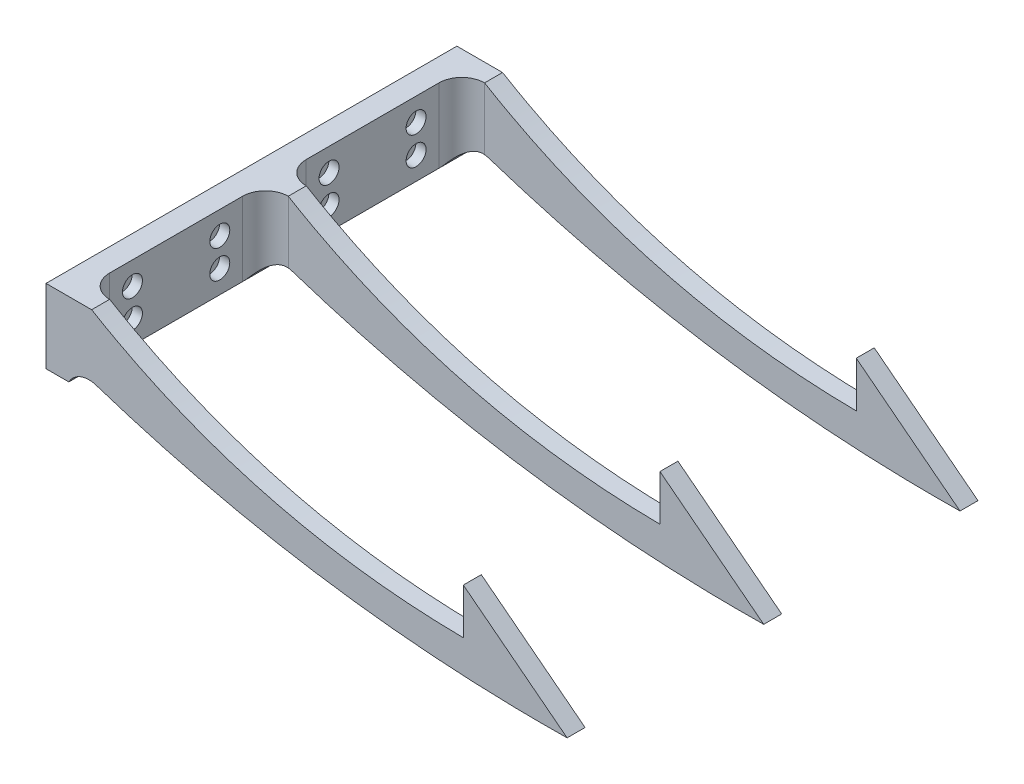
SolidWorks part; units mm, degrees
ref_plane "Front Plane" through (0, 0, 0) normal (0, 0, 1) x (1, 0, 0)
ref_plane "Top Plane" through (0, 0, 0) normal (0, 1, 0) x (1, 0, 0)
ref_plane "Right Plane" through (0, 0, 0) normal (1, 0, 0) x (0, 0, -1)
sketch "Sketch1" plane through (0, 0, 0) normal (0, 0, 1) x (1, 0, 0)
  line L0 (0, -6.35) -> (0, 6.35)
  line L1 (0, 6.35) -> (12.7, 6.35)
  line L2 (116.0939, -20.9749) -> (116.0939, -8.2749)
  line L3 (116.0939, -8.2749) -> (144.9605, -30.6605)
  line L5 (0, 12.7) -> (0, -12.7) construction
  line L6 (0, -12.7) -> (17.9605, -30.6605) construction
  line L7 (17.9605, -30.6605) -> (144.9605, -30.6605) construction
  spline S0 degree 2 poles (144.9605, -30.6605) (68.4115, -31.7178) (0, -6.35) knots 0 0 0 0.711551 0.711551 0.711551
  spline S1 degree 2 poles (116.0939, -20.9749) (57.7825, -20.4536) (12.7, 6.35) knots 0 0 0 0.666344 0.666344 0.666344
  dimension "D1" = 12.7
  dimension "D2" = 12.7
  dimension "D3" = 12.7
  dimension "D6" = 25.4
  dimension "D8" = 25.4
  dimension "D9" = 127
extrude "Boss-Extrude1" add sketch "Sketch1" along normal blind 5
sketch "Sketch2" plane through (0, 0, 5) normal (0, 0, 1) x (1, 0, 0)
  line L1 (0, 6.35) -> (6.35, 6.35)
  line L2 (0, 6.35) -> (0, -14.224)
  line L3 (0, -14.224) -> (6.35, -14.224)
  line L4 (6.35, 6.35) -> (6.35, -14.224)
  dimension "D1" = 20.574
  dimension "D2" = 6.35
extrude "Boss-Extrude2" add sketch "Sketch2" against normal blind 114.3
ref_plane "Plane1" through (0, 0, -52.15) normal (0, 0, 1) x (1, 0, 0)
mirror "Mirror1" about plane through (0, 0, -52.15) normal (0, 0, 1) of "Boss-Extrude1"
ref_plane "Plane2" through (0, 0, -24.845) normal (0, 0, 1) x (1, 0, 0)
mirror "Mirror3" about plane through (0, 0, -24.845) normal (0, 0, 1) of "Boss-Extrude1"
fillet "Fillet1" radius 6.35 7 edges at (6.35, -8.6416, -106.8) (6.35, -8.6416, -52.19) (6.35, -8.6416, 2.5) (6.35, -1.1458, -104.3) (6.35, -1.1458, -54.69) (6.35, -1.1458, -49.69) (6.35, -1.1458, 0)
hole_wizard "CBORE for #4 Socket Head Cap Screw1" positions "Sketch3" profile "Sketch4" counterbore size "#4" standard "ANSI Inch" end condition through all
sketch "Sketch3" plane through (6.35, 15.3303, -52.15) normal (1, 0, 0) x (0, 0, -1)
  point P0 (-39.45, -23.2043)
  point P2 (-15.16, -15.3303)
  point P13 (15.24, -23.2043)
  point P15 (39.45, -15.3303)
  point P26 (-39.45, -15.3303)
  point P28 (-15.16, -23.2043)
  point P30 (15.24, -15.3303)
  point P32 (39.45, -23.2043)
sketch "Sketch4" plane through (6.35, -7.874, -12.7) normal (0, 1, 0) x (0, 0, -1)
  line L0 (0, 0) -> (0, 6.35)
  line L1 (0, 6.35) -> (1.1303, 6.35)
  line L2 (1.1303, 6.35) -> (1.1303, 2.8448)
  line L3 (1.1303, 2.8448) -> (2.7788, 2.8448)
  line L4 (2.7788, 2.8448) -> (2.7788, 0)
  line L5 (2.7788, 0) -> (0, 0)
  line L6 (0, -6.35) -> (0, 107.95) construction
  dimension "Thru Hole Dia." = 2.2606
  dimension "Thru Hole Depth" = 6.35
  dimension "C'Bore Dia." = 5.5575
  dimension "C'Bore Depth" = 2.8448
